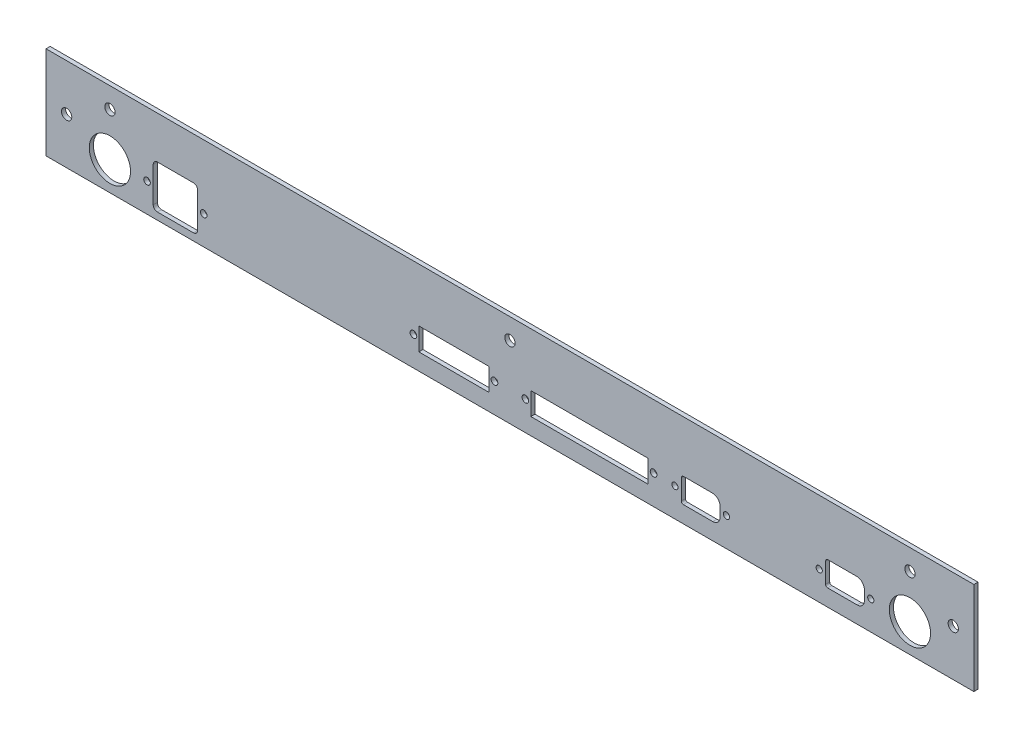
SolidWorks part; units mm, degrees
material "1345 Alloy"
ref_plane "Front Plane" through (0, 0, 0) normal (0, 0, 1) x (1, 0, 0)
ref_plane "Top Plane" through (0, 0, 0) normal (0, 1, 0) x (1, 0, 0)
ref_plane "Right Plane" through (0, 0, 0) normal (1, 0, 0) x (0, 0, -1)
sketch "Sketch1" plane through (0, 0, 0) normal (0, 0, 1) x (1, 0, 0)
  line L1 (-225, 22.5) -> (225, 22.5)
  line L2 (-225, 22.5) -> (-225, -22.5)
  line L3 (-225, -22.5) -> (225, -22.5)
  line L4 (225, 22.5) -> (225, -22.5)
  line L5 (-225, 22.5) -> (225, -22.5) construction
  line L6 (-225, -22.5) -> (225, 22.5) construction
  point P0 (0, 0)
  dimension "D1" = 450
  dimension "D2" = 45
extrude "Boss-Extrude1" add sketch "Sketch1" along normal blind 2
sketch "SK Terminal 12P cutout" plane through (0, 0, 0) normal (0, 0, 1) x (1, 0, 0)
  line L0 (10.125, -14.4) -> (67.045, -14.4)
  line L1 (67.045, -14.4) -> (67.045, -3.5)
  line L2 (67.045, -3.5) -> (10.125, -3.5)
  line L3 (10.125, -3.5) -> (10.125, -14.4)
  line L4 (69.67, 22.5) -> (69.67, -8.35) construction
  line L5 (225, 22.5) -> (-225, 22.5) construction
  line L6 (-7.5, -8.35) -> (-31.415, -8.35) construction
  line L7 (-44.185, -14.4) -> (-10.125, -14.4)
  line L8 (-10.125, -14.4) -> (-10.125, -3.5)
  line L9 (-10.125, -3.5) -> (-44.185, -3.5)
  line L10 (-44.185, -3.5) -> (-44.185, -14.4)
  line L11 (7.5, -8.35) -> (69.67, -8.35) construction
  line L12 (7.5, -8.35) -> (-7.5, -8.35) construction
  line L14 (-31.415, -8.35) -> (-31.415, -3.5) construction
  circle A0 centre (7.5, -8.35) radius 1.625
  circle A1 centre (69.67, -8.35) radius 1.625
  circle A2 centre (-46.81, -8.35) radius 1.625
  circle A3 centre (-7.5, -8.35) radius 1.625
  dimension "D1" = 62.17
  dimension "D2" = 15
extrude "Terminal 12P cutout" cut sketch "SK Terminal 12P cutout" against normal through all and the other way through all
sketch "Sketch2" plane through (0, 0, 2) normal (0, 0, 1) x (1, 0, 0)
  line L0 (-225, 22.5) -> (-215, 22.5) construction
  line L1 (-215, 22.5) -> (-215, 0) construction
  line L2 (-194, 12.4954) -> (194, 12.4954) construction
  line L3 (0, 22.5) -> (0, 12.5) construction
  circle A0 centre (-215, 0) radius 2.5
  circle A1 centre (215, 0) radius 2.5
  circle A2 centre (-194, 12.4954) radius 2.5
  circle A3 centre (194, 12.4954) radius 2.5
  circle A4 centre (0, 12.5) radius 2.5
  dimension "D3" = 5
  dimension "D4" = 5
  dimension "D5" = 5
  dimension "D7" = 5
  dimension "D8" = 5
  dimension "D1" = 10
  dimension "D2" = 22.5
  dimension "D6" = 10
extrude "Cut-Extrude1" cut sketch "Sketch2" against normal through all
sketch "Sketch3" plane through (0, 0, 2) normal (0, 0, 1) x (1, 0, 0)
  line L0 (175, -8.55) -> (225, -8.55) construction
  line L5 (168.375, -14.4) -> (154.1, -14.4)
  line L6 (154.3, -2.5) -> (168.175, -2.5)
  line L7 (153.1, -13.4) -> (153.1, -3.7)
  line L8 (171.9, -10.875) -> (171.9, -6.225)
  line L13 (171.9, -8.55) -> (175, -8.55) construction
  line L14 (194, 12.4954) -> (194, -8.55) construction
  line L15 (225, -22.5) -> (225, 22.5) construction
  line L16 (150, -8.55) -> (153.1, -8.55) construction
  line L17 (98.375, -14.4) -> (84.1, -14.4)
  line L18 (150, -8.55) -> (153.1, -8.55) construction
  line L19 (84.3, -2.5) -> (98.175, -2.5)
  line L20 (83.1, -13.4) -> (83.1, -3.7)
  line L21 (101.9, -10.875) -> (101.9, -6.225)
  line L22 (101.9, -8.55) -> (105, -8.55) construction
  line L23 (80, -8.55) -> (83.1, -8.55) construction
  line L24 (80, -8.55) -> (83.1, -8.55) construction
  line L25 (150, -8.55) -> (105, -8.55) construction
  line L27 (194, -8.55) -> (194, -22.5) construction
  line L28 (-225, -22.5) -> (225, -22.5) construction
  line L29 (194, -22.5) -> (225, -22.5) construction
  line L30 (-194, -8.55) -> (-194, -22.5) construction
  line L31 (-225, -22.5) -> (-194, -22.5) construction
  line L32 (-194, -8.55) -> (-176, -8.55) construction
  line L33 (-171, -19.05) -> (-153.5, -19.05)
  line L34 (-151.5, -17.05) -> (-151.5, -0.05)
  line L35 (-153.5, 1.95) -> (-171, 1.95)
  line L36 (-173, -0.05) -> (-173, -17.05)
  line L37 (-171, -0.05) -> (-153.5, -17.05) construction
  line L39 (-153.5, -0.05) -> (-171, -17.05) construction
  line L40 (-194, -8.55) -> (-225, -8.55) construction
  line L42 (-176, -8.55) -> (-162.25, -8.55) construction
  line L43 (-162.25, -8.55) -> (-148.5, -8.55) construction
  line L44 (-225, 22.5) -> (-225, -22.5) construction
  line L45 (-225, -8.55) -> (-225, -22.5) construction
  arc A4 (171.9, -10.875) -> (168.375, -14.4) centre (168.375, -10.875) cw
  arc A5 (171.9, -6.225) -> (168.175, -2.5) centre (168.175, -6.225) ccw
  arc A6 (154.1, -14.4) -> (153.1, -13.4) centre (154.1, -13.4) cw
  arc A7 (153.1, -3.7) -> (154.3, -2.5) centre (154.3, -3.7) cw
  circle A14 centre (150, -8.55) radius 1.5
  circle A15 centre (175, -8.55) radius 1.5
  arc A16 (101.9, -10.875) -> (98.375, -14.4) centre (98.375, -10.875) cw
  arc A17 (101.9, -6.225) -> (98.175, -2.5) centre (98.175, -6.225) ccw
  arc A18 (84.1, -14.4) -> (83.1, -13.4) centre (84.1, -13.4) cw
  arc A19 (83.1, -3.7) -> (84.3, -2.5) centre (84.3, -3.7) cw
  circle A20 centre (80, -8.55) radius 1.5
  circle A21 centre (105, -8.55) radius 1.5
  circle A22 centre (194, -8.55) radius 10
  circle A23 centre (-194, -8.55) radius 10
  arc A24 (-153.5, -19.05) -> (-151.5, -17.05) centre (-153.5, -17.05) ccw
  arc A25 (-151.5, -0.05) -> (-153.5, 1.95) centre (-153.5, -0.05) ccw
  arc A26 (-171, 1.95) -> (-173, -0.05) centre (-171, -0.05) ccw
  arc A27 (-173, -17.05) -> (-171, -19.05) centre (-171, -17.05) ccw
  circle A28 centre (-176, -8.55) radius 1.6
  circle A29 centre (-148.5, -8.55) radius 1.6
  dimension "D3" = 3
  dimension "D4" = 3
  dimension "D5" = 3
  dimension "D6" = 3
  dimension "D7" = 25
  dimension "D11" = 20
  dimension "D2" = 50
  dimension "D8" = 5.85
  dimension "D9" = 45
  dimension "D10" = 25
  dimension "D12" = 31
  dimension "D13" = 5.85
  dimension "D14" = 31
  dimension "D15" = 27.5
  dimension "D17" = 13.75
  dimension "D19" = 18
extrude "Cut-Extrude2" cut sketch "Sketch3" against normal blind 10
